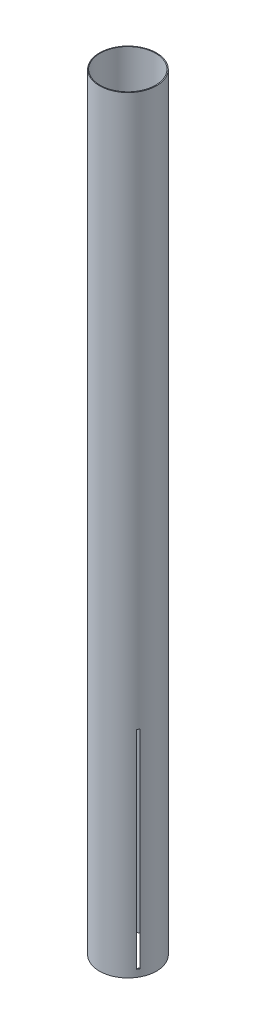
SolidWorks part; units mm, degrees
ref_plane "Front Plane" through (0, 0, 0) normal (0, 0, 1) x (1, 0, 0)
ref_plane "Top Plane" through (0, 0, 0) normal (0, 1, 0) x (1, 0, 0)
ref_plane "Right Plane" through (0, 0, 0) normal (1, 0, 0) x (0, 0, -1)
sketch "Sketch1" plane through (0, 0, 0) normal (0, 1, 0) x (1, 0, 0)
  circle A0 centre (0, 0) radius 51
  circle A1 centre (-0.3423, 0) radius 49.55
  dimension "D1" = 102
  dimension "D2" = 99.1
extrude "Boss-Extrude1" add sketch "Sketch1" along normal blind 1370
sketch "Sketch2" plane through (0, 0, 0) normal (0, 0, 1) x (1, 0, 0)
  line L0 (0, 12.7) -> (2.38, 12.7)
  line L1 (2.38, 12.7) -> (2.38, 383.7)
  line L2 (2.38, 383.7) -> (-2.38, 383.7)
  line L3 (-2.38, 383.7) -> (-2.38, 12.7)
  line L4 (-2.38, 12.7) -> (0, 12.7)
  line L5 (0, 1370) -> (0, 0) construction
  line L6 (-51, 0) -> (51, 0) construction
  dimension "D1" = 4.76
  dimension "D2" = 2.38
  dimension "D3" = 0
  dimension "D4" = 371
  dimension "D5" = 12.7
extrude "Cut-Extrude1" cut sketch "Sketch2" against normal through all
pattern_circular "CirPattern1" count 3 over 360 about axis through (0, 0, 0) along (0, 1, 0) of "Cut-Extrude1"
